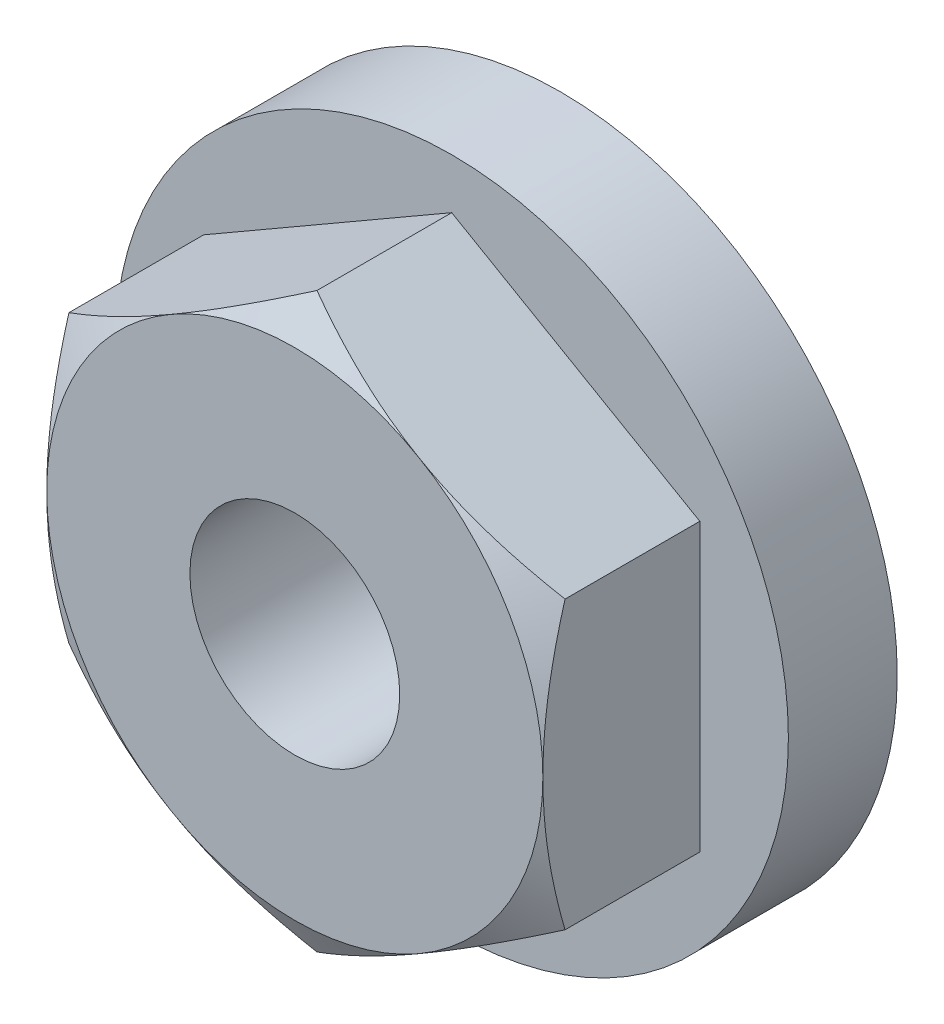
SolidWorks part; units mm, degrees
ref_plane "Front Plane" through (0, 0, 0) normal (0, 0, 1) x (1, 0, 0)
ref_plane "Top Plane" through (0, 0, 0) normal (0, 1, 0) x (1, 0, 0)
ref_plane "Right Plane" through (0, 0, 0) normal (1, 0, 0) x (0, 0, -1)
sketch "Sketch1" plane through (0, 0, 0) normal (0, 0, 1) x (1, 0, 0)
  line L1 (0, 6.4158) -> (-5.5563, 3.2079)
  line L2 (-5.5563, 3.2079) -> (-5.5563, -3.2079)
  line L3 (-5.5563, -3.2079) -> (0, -6.4158)
  line L4 (0, -6.4158) -> (5.5562, -3.2079)
  line L5 (5.5562, -3.2079) -> (5.5562, 3.2079)
  line L6 (5.5562, 3.2079) -> (0, 6.4158)
  circle A0 centre (0, 0) radius 5.5563 construction
  dimension "Hex" = 11.1125
extrude "Extrude1" add sketch "Sketch1" against normal blind 5.9531
sketch "Sketch13" plane through (0, 0, -5.9531) normal (0, 0, -1) x (-1, 0, 0)
  circle A0 centre (0, 0) radius 7.5406
  dimension "Flange od" = 15.0812
extrude "Extrude3" add sketch "Sketch13" against normal blind 2.4384
sketch "Sketch2" plane through (0, 0, 0) normal (0, 0, 1) x (1, 0, 0)
  circle A0 centre (0, 0) radius 5.5563 construction
  circle A1 centre (0, 0) radius 5.5563
extrude "Cut-Extrude1" cut sketch "Sketch2" against normal through all draft 60 flip side to cut
sketch "Sketch4" plane through (0, 0, 0) normal (0, 0, 1) x (1, 0, 0)
  circle A0 centre (0, 0) radius 3.175
  dimension "Thread Dia" = 6.35
extrude "Cut-Extrude3" cut sketch "Sketch4" against normal through all
sketch "Sketch7" plane through (0, 0, 0) normal (0, 0, 1) x (1, 0, 0)
  circle A4 centre (0, 0) radius 3.429
  circle A5 centre (0, 0) radius 3.429
  dimension "D1" = 0.254
sketch "Sketch8" plane through (0, 0, -5.9531) normal (0, 0, -1) x (-1, 0, 0)
  circle A1 centre (0, 0) radius 3.429
  circle A2 centre (0, 0) radius 3.429 construction
sketch "Sketch5" plane through (0, 0, 0) normal (0, 0, 1) x (1, 0, 0)
  circle A0 centre (0, 0) radius 3.175 construction
  circle A1 centre (0, 0) radius 3.175
curve "Helix/Spiral1" pitch 1.27 height 7.2231 turns 5.6875 parameters "pitch"=1.27
sketch "Sketch9" plane through (0, 0, 0) normal (1, 0, 0) x (0, 0, -1)
  line L0 (-0.635, 3.175) -> (-0.4762, 3.175)
  line L1 (-0.4762, 3.175) -> (0, 2.3501)
  line L2 (-0.635, 3.175) -> (-1.1112, 2.3501)
  line L3 (-1.1112, 2.3501) -> (0, 2.3501)
  line L4 (-0.5556, 3.175) -> (-0.5556, 2.3501) construction
  line L5 (-0.8731, 2.7626) -> (-0.2381, 2.7626) construction
  line L7 (0, 2.3501) -> (0, 3.175) construction
  line L8 (0, 3.175) -> (0, -3.175) construction
  dimension "D1" = 0.1588
  dimension "D2" = 0.635
  dimension "D3" = 60
sketch "Sketch12" plane through (0, 0, 0) normal (0, 0, 1) x (1, 0, 0)
  circle A0 centre (0, 0) radius 2.3501
  circle A1 centre (0, 0) radius 3.175 construction
  circle A2 centre (0, 0) radius 3.175
extrude "Extrude2" add sketch "Sketch12" against normal up to surface (5.9531 mm away) up to face at (3.175, 0, -5.9531)
sweep "Cut-Sweep1" [suppressed] cut profiles "Sketch9" path "Helix/Spiral1"
extrude "Cut-Extrude6" [suppressed] cut sketch "Sketch7" against normal through all draft 45
extrude "Cut-Extrude7" [suppressed] cut sketch "Sketch8" against normal through all draft 45
sketch "Sketch14" [suppressed] plane through (0, 0, -5.9531) normal (0, 0, -1) x (-1, 0, 0)
  circle A4 centre (0, 0) radius 5.461
  circle A5 centre (0, 0) radius 5.461
  dimension "D1" = 2.032
extrude "Cut-Extrude8" [suppressed] cut sketch "Sketch14" against normal blind 0.2438 flip side to cut
sketch "Sketch15" [suppressed] plane through (0, 0, -5.7093) normal (0, 0, -1) x (-1, 0, 0)
  line L0 (-0.5353, 5.4347) -> (-0.7391, 7.5043)
  line L1 (0.5353, 5.4347) -> (0.7391, 7.5043)
  line L2 (0, 0) -> (0.5353, 5.4347) construction
  line L3 (0, 0) -> (-0.5353, 5.4347) construction
  circle A0 centre (0, 0) radius 7.5406 construction
  circle A1 centre (0, 0) radius 5.461 construction
  arc A2 (0.7391, 7.5043) -> (-0.7391, 7.5043) centre (0, 0) ccw
  arc A3 (0.5353, 5.4347) -> (-0.5353, 5.4347) centre (0, 0) ccw
  dimension "D1" = 11.25
extrude "Extrude4" [suppressed] add sketch "Sketch15" along normal up to surface (0.2438 mm away) separate body
sketch "Sketch16" [suppressed] plane through (0, 0, 0) normal (0, 1, 0) x (1, 0, 0)
  line L0 (-0.7391, 5.7093) -> (0.7391, 5.9531)
  line L4 (-0.7391, 5.7093) -> (0.7391, 5.7093)
  line L5 (0.7391, 5.7093) -> (0.7391, 5.9531)
  line L6 (0.7391, 5.9531) -> (-0.7391, 5.9531)
  line L7 (-0.7391, 5.9531) -> (-0.7391, 5.7093)
  line L8 (-0.7391, 5.7093) -> (0.7391, 5.7093) construction
  line L9 (0.7391, 5.7093) -> (0.7391, 5.9531) construction
  line L10 (0.7391, 5.9531) -> (-0.7391, 5.9531)
  line L11 (-0.7391, 5.9531) -> (-0.7391, 5.7093)
  dimension "D1" = 0
extrude "Cut-Extrude9" [suppressed] cut sketch "Sketch16" along normal through all
pattern_circular "CirPattern1" [suppressed] count 32 over 360 of bodies 119
combine bodies "Combine1" [suppressed] operation type add bodies to combine 117 119 120 121 122 123 124 125 126 127 128 129 130 131 132 133 134 135 136 137 139 140 141 142 143 144 145 146 147 148 149 150 151 152 153 154 155
sketch "Sketch17" [suppressed] plane through (0, 0, 0) normal (1, 0, 0) x (0, 0, -1)
  line L0 (5.9531, 7.5406) -> (5.9531, -7.5406) construction
  line L1 (3.5147, 7.5406) -> (3.5147, -7.5406) construction
  dimension "D1" = 2.4384
sketch "Sketch18" plane through (0, 0, -3.5147) normal (0, 0, 1) x (1, 0, 0)
  circle A0 centre (0, 0) radius 7.5406
  circle A1 centre (0, 0) radius 7.5406 construction
equation "\"D2@Sketch9\" = \"pitch@Helix/Spiral1\"*.5"
equation "\"D3@Helix/Spiral1\" = \"pitch@Helix/Spiral1\"+\"Height@Extrude1\""
equation "\"D1@Sketch9\" = \"pitch@Helix/Spiral1\"*.125"
equation "\"D1@Cut-Extrude8\" = \"flange thickness@Extrude3\"*.1"
equation "\"D1@Sketch17\" = \"flange thickness@Extrude3\""
